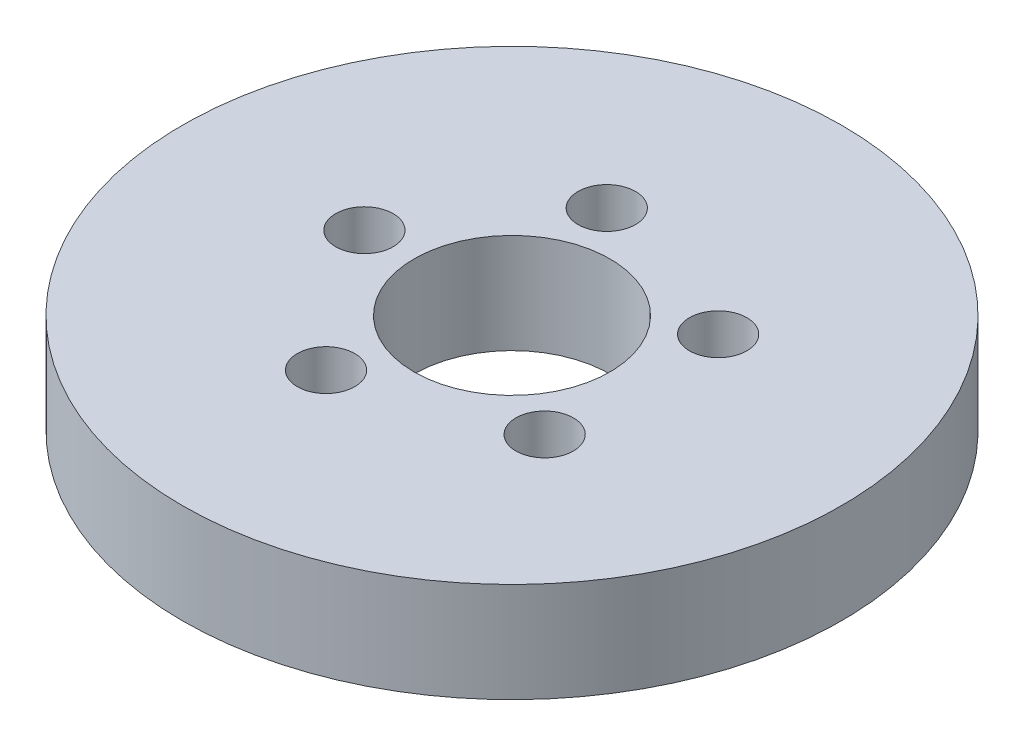
SolidWorks part; units mm, degrees
ref_plane "Front Plane" through (0, 0, 0) normal (0, 0, 1) x (1, 0, 0)
ref_plane "Top Plane" through (0, 0, 0) normal (0, 1, 0) x (1, 0, 0)
ref_plane "Right Plane" through (0, 0, 0) normal (1, 0, 0) x (0, 0, -1)
sketch "Sketch1" plane through (0, 0, 0) normal (0, 1, 0) x (1, 0, 0)
  circle A0 centre (0, 0) radius 92.5
  dimension "FLANGE_OD" = 185
extrude "Boss-Extrude1" add sketch "Sketch1" along normal blind 28
sketch "Sketch2" plane through (0, 0, 0) normal (0, 1, 0) x (1, 0, 0)
  circle A0 centre (0, 0) radius 27.5
  dimension "BORE_D" = 55
extrude "Cut-Extrude1" cut sketch "Sketch2" along normal through all
sketch "Sketch3" plane through (0, 28, 0) normal (0, 1, 0) x (1, 0, 0)
  circle A0 centre (0, 0) radius 41.427 construction
  circle A1 centre (-41.427, 0) radius 8.0672
  dimension "BOLT_D" = 16.1345
  dimension "BOLT_PCD" = 82.8539
extrude "Cut-Extrude2" cut sketch "Sketch3" against normal blind 21.626
pattern_circular "CirPattern1" count 5 over 360 about axis through (0, 0, 0) along (0, 1, 0) of "Cut-Extrude2"
